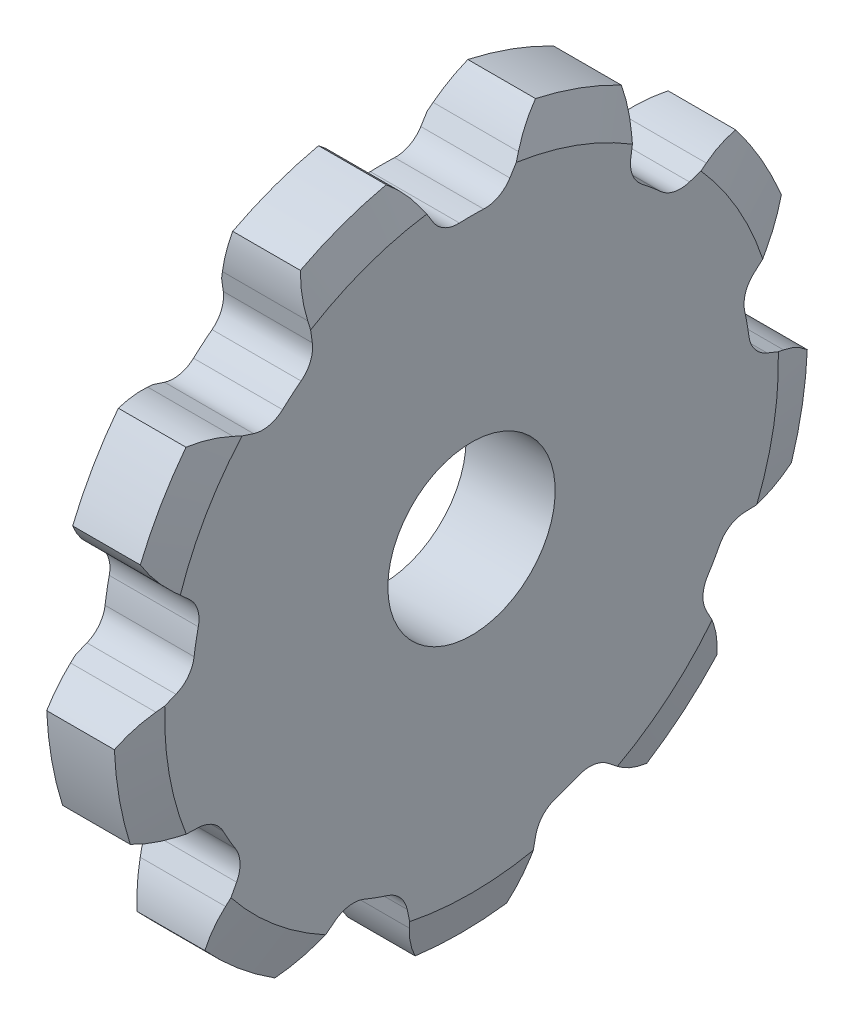
SolidWorks part; units mm, degrees
ref_plane "Plane1" through (0, 0, 0) normal (0, 0, 1) x (1, 0, 0)
ref_plane "Plane2" through (0, 0, 0) normal (0, 1, 0) x (1, 0, 0)
ref_plane "Plane3" through (0, 0, 0) normal (1, 0, 0) x (0, 0, -1)
sketch "Clipboard" plane through (0, 0, 0) normal (0, 1, 0) x (1, 0, 0)
  line L0 (0, 0) -> (65.4527, -10.3667)
  line L1 (-15, 0) -> (100, 0) construction
  line L2 (0, 0) -> (-2.1039, 2.3779)
  line L3 (0, 0) -> (-11.863, 4.5341)
  line L4 (0, 0) -> (8.5297, 1.351)
  line L5 (0, 0) -> (-71.3958, -26.6285)
  line L6 (0, 0) -> (-22.4032, -15.1155)
  line L7 (-2.1039, 2.3779) -> (14.2981, 76.7917)
  line L8 (-76.2, 54.61) -> (-19.7358, 54.61)
  line L9 (-66.6514, 23.5599) -> (-55.7196, 25.8835)
  line L10 (-76.2, 71.12) -> (20.6782, 71.12)
  line L11 (0, 0) -> (-28.448, 0)
  line L12 (-76.2, 101.6) -> (-47.752, 101.6)
  circle A0 centre (0, 0) radius 11.176
  circle A1 centre (0, 0) radius 25.4
  circle A2 centre (0, 0) radius 25.4
  dimension "Num_teeth" = 9
  dimension "Pitch_radius" = 96.8782
  dimension "Width" = 28.448
  dimension "F" = 28.448
  dimension "H" = 11.176
  dimension "Thickness" = 27.0256
sketch "BasProSke" plane through (0, 0, 0) normal (0, 1, 0) x (1, 0, 0)
  line L0 (-10, 0) -> (60, 0) construction
  line L1 (0, 0) -> (0, 93.1564)
  line L2 (0, 0) -> (27.0256, 0)
  line L3 (27.0256, 0) -> (27.0256, 93.1564)
  line L4 (23.7825, 105.2597) -> (3.2431, 105.2597)
  line L5 (0, 93.1564) -> (3.2431, 105.2597)
  line L6 (27.0256, 93.1564) -> (23.7825, 105.2597)
  dimension "Thickness" = 27.0256
  dimension "Diameter" = 210.5195
  dimension "D1" = 15
  dimension "D2" = 15
revolve "Base-Revolve" add sketch "BasProSke" angle 360 about L0
sketch "TooCutSke" plane through (0, 0, 0) normal (1, 0, 0) x (0, 0, -1)
  line L0 (-11.6391, 89.0554) -> (-14.7996, 94.1133)
  line L1 (0, 0) -> (0, 107) construction
  line L2 (3.3134, 0) -> (3.3134, 129.2389) construction
  line L3 (11.6391, 89.0554) -> (14.7996, 94.1133)
  line L4 (39.8732, 109.5507) -> (44.2168, 121.4848)
  line L5 (3.3134, 101.2907) -> (51.8809, 70.9424) construction
  line L6 (-39.8732, 109.5507) -> (-44.2168, 121.4848)
  arc A0 (3.6705, 84.8609) -> (-3.6705, 84.8609) centre (0, 0) ccw
  arc A1 (3.6705, 84.8609) -> (11.6391, 89.0554) centre (4.0569, 93.7933) ccw
  arc A2 (-3.6705, 84.8609) -> (-11.6391, 89.0554) centre (-4.0569, 93.7933) cw
  circle A3 centre (0, 0) radius 96.8782 construction
  circle A4 centre (3.3134, 96.8215) radius 11.176 construction
  arc A5 (14.7996, 94.1133) -> (39.8732, 109.5507) centre (42.8991, 76.5548) cw
  arc A6 (-14.7996, 94.1133) -> (-39.8732, 109.5507) centre (-42.8991, 76.5548) ccw
  arc A7 (44.2168, 121.4848) -> (-44.2168, 121.4848) centre (0, 0) ccw
  dimension "Pitch_radius" = 96.8782
  dimension "R" = 8.9408
  dimension "H" = 11.176
  dimension "Ag" = 64
  dimension "Angle" = 40
extrude "ToothCut" cut sketch "TooCutSke" along normal through all
pattern_circular "TeethCuts" count 9 every 40 about axis through (-10, 0, 0) along (1, 0, 0) of "ToothCut"
sketch "HubNeaOneSke" plane through (0, 0, 0) normal (-1, 0, 0) x (0, 0, 1)
  circle A0 centre (0, 0) radius 25.4
  dimension "Diameter" = 50.8
extrude "HubNearOne" [suppressed] add sketch "HubNeaOneSke" along normal blind 49.1745
sketch "HubNeaBotSke" plane through (0, 0, 0) normal (-1, 0, 0) x (0, 0, 1)
  circle A0 centre (0, 0) radius 25.4
  dimension "Diameter" = 50.8
extrude "HubNearBoth" [suppressed] add sketch "HubNeaBotSke" along normal blind 24.5872
ref_plane "FarPln" through (27.0256, 0, 0) normal (1, 0, 0) x (0, 0, -1)
sketch "HubFarSke" plane through (27.0256, 0, 0) normal (1, 0, 0) x (0, 0, -1)
  circle A0 centre (0, 0) radius 25.4
  dimension "Diameter" = 50.8
extrude "HubFar" [suppressed] add sketch "HubFarSke" along normal blind 24.5872
sketch "BorSke" plane through (0, 0, 0) normal (1, 0, 0) x (0, 0, -1)
  circle A0 centre (0, 0) radius 25.4
  dimension "Diameter" = 50.8
extrude "Bore" cut sketch "BorSke" along normal mid plane 152.4001
sketch "KeySke" plane through (0, 0, 0) normal (1, 0, 0) x (0, 0, -1)
  line L0 (-6.35, 0) -> (-6.35, 31.0642)
  line L1 (-6.35, 31.0642) -> (6.35, 31.0642)
  line L2 (6.35, 31.0642) -> (6.35, 0)
  line L3 (0, 0) -> (0, 34) construction
  line L4 (-6.35, 0) -> (6.35, 0)
  dimension "Width" = 12.7
extrude "Keyway" [suppressed] cut sketch "KeySke" along normal mid plane 152.4001
pattern_circular "Keyway2" [suppressed] count 2 every 90 about axis through (-10, 0, 0) along (1, 0, 0) reverse direction yes
equation "\"Thickness@Clipboard\" = \"Width@Clipboard\" * 0.95"
equation "\"H@Clipboard\" = \"Diameter@Clipboard\" / 2.0"
equation "\"OAL@Clipboard\" = \"Thickness@Clipboard\""
equation "\"Pitch_radius@Clipboard\" = ( \"Pitch@Clipboard\" / 2.0) / sin(3.14159265 / \"Num_teeth@Clipboard\" )"
equation "\"MHD@Clipboard\" = (1.0 / tan(3.14159265 / \"Num_teeth@Clipboard\" ) - 0.05) * \"Pitch@Clipboard\" - \"F@Clipboard\""
equation "\"MHD@Clipboard\" = ((sgn( \"MHD@Clipboard\" - \"Hub_dia@Clipboard\" )-1)*( \"MHD@Clipboard\" - \"Hub_dia@Clipboard\" ))/-2+ \"Hub_dia@Clipboard\""
equation "\"OAL@Clipboard\" = ((sgn( \"OAL@Clipboard\" - \"Overall_len@Clipboard\" )+1)*( \"OAL@Clipboard\" - \"Overall_len@Clipboard\" ))/2 + \"Overall_len@Clipboard\" + 0.000002"
equation "\"Num_teeth@TeethCuts\" = int( \"Show_teeth@Clipboard\" ) + 1"
equation "\"Num_teeth@TeethCuts\" = ((sgn( \"Num_teeth@TeethCuts\" - \"Num_teeth@Clipboard\" )-1)*( \"Num_teeth@TeethCuts\" - \"Num_teeth@Clipboard\" ))/-2+ \"Num_teeth@Clipboard\""
equation "\"Num_teeth@TeethCuts\" = ((sgn( \"Num_teeth@TeethCuts\" - 2.0)+1)*( \"Num_teeth@TeethCuts\" - 2.0))/2 +2.0"
equation "\"Angle@TeethCuts\" = 360.0 / \"Num_teeth@Clipboard\""
equation "\"Pitch_radius@TooCutSke\" = \"Pitch_radius@Clipboard\""
equation "\"Cp@TooCutSke\" = 0.05 * \"Pitch@Clipboard\""
equation "\"Rt@TooCutSke\" = 0.5 * \"Pitch@Clipboard\""
equation "\"R@TooCutSke\"  = 0.8 * \"H@Clipboard\""
equation "\"Db@TooCutSke\" = \"Pitch_radius@Clipboard\" - \"H@Clipboard\" - 0.03"
equation "\"Ag@TooCutSke\" =  2.0 * \"Ap@Clipboard\" + 360.0 / \"Num_teeth@Clipboard\""
equation "\"H@TooCutSke\" = \"H@Clipboard\""
equation "\"Angle@TooCutSke\" =  360.0 / \"Num_teeth@Clipboard\""
equation "\"Wf@TooCutSke\" = 0.01 * \"Pitch@Clipboard\" * \"Num_teeth@Clipboard\""
equation "\"Wf@TooCutSke\" = ((sgn( \"Wf@TooCutSke\" - \"H@Clipboard\" * 0.8 )-1)*( \"Wf@TooCutSke\" - \"H@Clipboard\" * 0.8 ))/-2+ \"H@Clipboard\" * 0.8"
equation "\"Diameter@BasProSke\" = (1.0 / tan(3.14159265 / \"Num_teeth@Clipboard\" )) * \"Pitch@Clipboard\" + \"F@Clipboard\""
equation "\"Thickness@BasProSke\"  = \"Thickness@Clipboard\""
equation "\"G1@BasProSke\" =  \"Thickness@Clipboard\" * 0.12"
equation "\"G2@BasProSke\" =   \"Thickness@Clipboard\" * 0.12"
equation "\"MHD@Clipboard\" = ((sgn( \"MHD@Clipboard\" - \"Db@TooCutSke\" * 2.0  )-1)*( \"MHD@Clipboard\" - \"Db@TooCutSke\" * 2.0 ))/-2+ \"Db@TooCutSke\" * 2.0"
equation "\"Diameter@HubNeaOneSke\" = \"MHD@Clipboard\""
equation "\"Length@HubNearOne\" = \"OAL@Clipboard\" - \"Thickness@BasProSke\""
equation "\"Diameter@HubNeaBotSke\" = \"MHD@Clipboard\""
equation "\"Length@HubNearBoth\" = ( \"OAL@Clipboard\" - \"Thickness@BasProSke\" ) / 2.0"
equation "\"Thickness@FarPln\" = \"Thickness@BasProSke\""
equation "\"Diameter@HubFarSke\" = \"MHD@Clipboard\""
equation "\"Length@HubFar\" = ( \"OAL@Clipboard\" - \"Thickness@BasProSke\" ) / 2.0"
equation "\"D1@Bore\" = \"OAL@Clipboard\" * 2.0"
equation "\"D1@Keyway\" = \"OAL@Clipboard\" * 2.0"
equation "\"Offset@KeySke\" = \"T_dim@Clipboard\" - \"Diameter@BorSke\" / 2.0"
